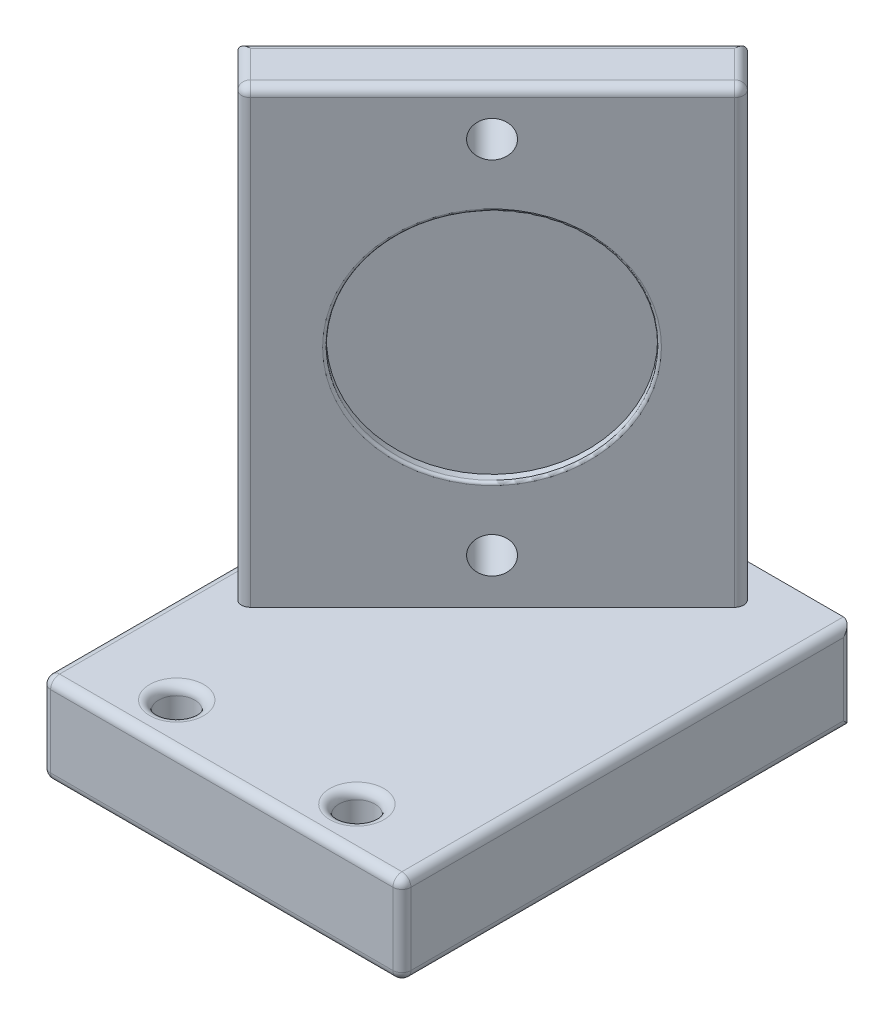
SolidWorks part; units mm, degrees
note: The reader was unsure of these and kept them because the rebuilt part matched: shared geometry of "草图1<3>", "草图2<3>".
ref_plane "前视基准面" through (0, 0, 0) normal (0, 0, 1) x (1, 0, 0)
ref_plane "上视基准面" through (0, 0, 0) normal (0, 1, 0) x (1, 0, 0)
ref_plane "右视基准面" through (0, 0, 0) normal (1, 0, 0) x (0, 0, -1)
sketch "草图1" plane through (0, 0, 0) normal (0, 1, 0) x (1, 0, 0)
  line L1 (-23.2618, 28.7827) -> (-9.1197, 42.9248)
  line L3 (-17.4339, -7.1052) -> (-17.4339, -2.1052)
  line L4 (-17.4339, -7.1052) -> (-37.4339, -7.1052)
  line L5 (-23.2618, 28.7827) -> (-37.4039, 14.6405)
  line L6 (-17.4339, -2.1052) -> (-27.4339, -2.1052)
  line L7 (-17.4339, -2.1052) -> (-7.4339, -2.1052)
  line L8 (-9.1197, 42.9248) -> (-4.676, 38.4812)
  line L9 (-4.676, 38.4812) -> (-32.9603, 10.1969)
  line L10 (-32.9603, 10.1969) -> (-37.4039, 14.6405)
  line L11 (2.5661, 42.8948) -> (-10.5869, 42.8948)
  line L12 (-37.4339, 2.8948) -> (-37.4339, 15.8948)
  line L13 (-37.4339, 15.8948) -> (-10.5869, 42.8948)
  line L14 (-37.4339, -7.1052) -> (-37.4339, 2.8948)
  line L15 (-17.4339, -7.1052) -> (2.5661, -7.1052)
  line L16 (2.5661, -7.1052) -> (2.5661, 42.8948)
  circle A0 centre (-7.4339, -2.1052) radius 2
  circle A1 centre (-27.4339, -2.1052) radius 2
extrude "凸台-拉伸1" add sketch "草图1" along normal blind 10
extrude "凸台-拉伸2" add sketch "草图1<3>" along normal blind 60
sketch "草图1<3>" plane through (0, 0, 0) normal (0, 1, 0) x (1, 0, 0) same geometry as "草图1"
sketch "草图2" plane through (-21.5786, 0, -21.5786) normal (0.7071, 0, 0.7071) x (0.7071, 0, -0.7071)
  circle A0 centre (3.8614, 35) radius 13
  circle A1 centre (3.8614, 55) radius 2
  circle A2 centre (3.8614, 15) radius 2
extrude "切除-拉伸1" cut sketch "草图2" against normal blind 1.1
fillet "圆角1" radius 0.3 1 edges at (-9.6557, 35, -33.5014)
fillet "圆角2" radius 1 18 edges at (2.5661, 5, -42.8948) (2.5661, 0, -17.8948) (2.5661, 10, -17.8948) (-37.4339, 5, -15.8948) (-37.4339, 10, -4.3948) (-37.4339, 0, -4.3948) (-37.4339, 5, 7.1052) (-17.4339, 10, 7.1052) (2.5661, 5, 7.1052) (-17.4339, 0, 7.1052) (-4.676, 35, -38.4812) (-23.2618, 60, -28.7827) (-6.8979, 60, -40.703) (-18.8182, 60, -24.339) (-35.1821, 60, -12.4187) (-32.9603, 35, -10.1969) (-7.4339, 10, 4.1052) (-27.4339, 10, 4.1052)
extrude "切除-拉伸2" cut sketch "草图2<3>" against normal through all contours A1 | A2
sketch "草图2<3>" plane through (-21.5786, 0, -21.5786) normal (0.7071, 0, 0.7071) x (0.7071, 0, -0.7071) same geometry as "草图2"
